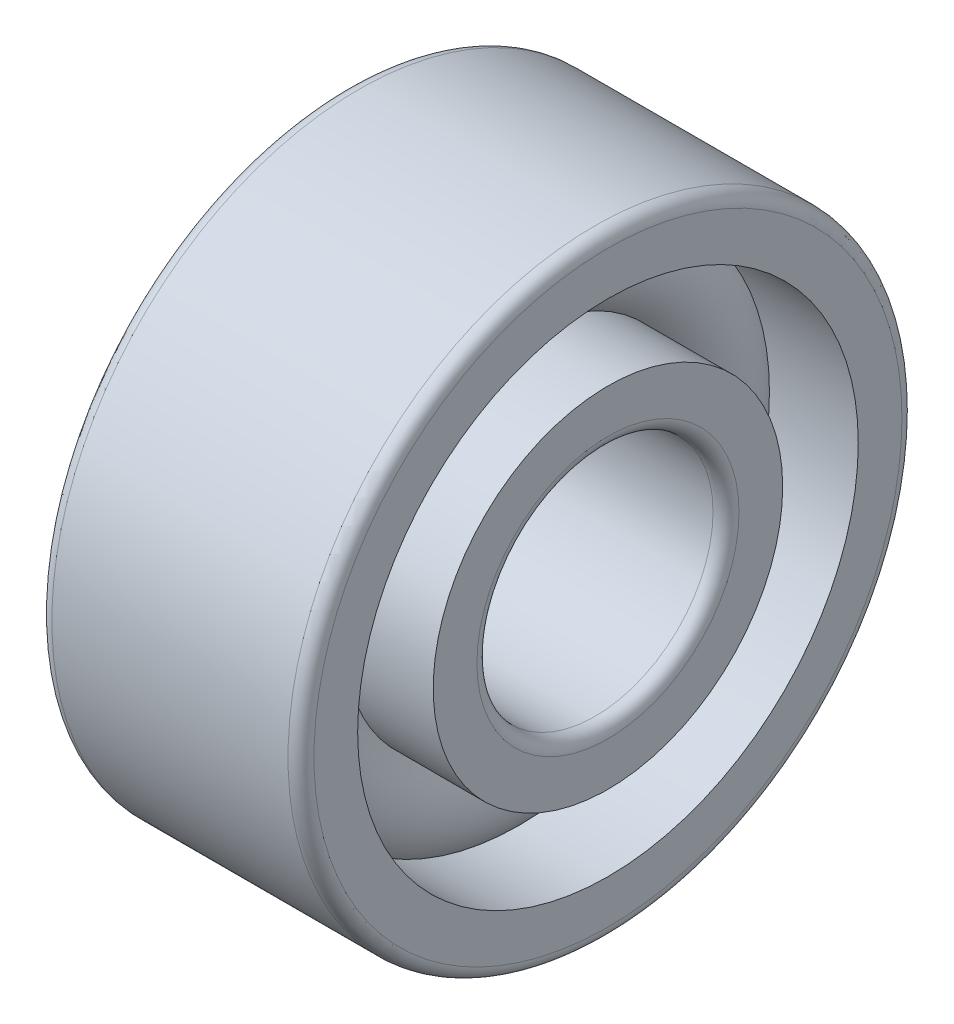
SolidWorks part; units mm, degrees
ref_plane "Plane1" through (0, 0, 0) normal (0, 0, 1) x (1, 0, 0)
ref_plane "Plane2" through (0, 0, 0) normal (0, 1, 0) x (1, 0, 0)
ref_plane "Plane3" through (0, 0, 0) normal (1, 0, 0) x (0, 0, -1)
sketch "Clipboard" plane through (0, 0, 0) normal (0, 0, 1) x (1, 0, 0)
  line L0 (-10, 0) -> (10, 0) construction
  line L1 (0, 0) -> (22.3471, -0.7804)
  line L2 (0, 0) -> (17.989, 0.6282)
  line L3 (0, 0) -> (22.3471, -0.7804)
  line L4 (0, 0) -> (-22.3573, -0.3902)
  dimension "BallCLRad" = 18
sketch "CagSpiSke" plane through (0, 0, 0) normal (0, 0, 1) x (1, 0, 0)
  line L0 (0.48, 17.2) -> (0.48, 18.8)
  line L1 (0.48, 18.8) -> (-0.48, 18.8)
  line L2 (-0.48, 18.8) -> (-0.48, 17.2)
  line L3 (-0.48, 17.2) -> (0.48, 17.2)
  line L4 (-20.6375, 0) -> (20.6375, 0) construction
  line L5 (0, 0) -> (0, 23.7692) construction
  dimension "OD" = 37.6
  dimension "ID" = 34.4
revolve "CageSpine" add sketch "CagSpiSke" angle 0.001 about L4 reverse direction yes
ref_axis "Axis1" through (-50, 0, 0) along (1, 0, 0)
sketch "CagBalSke" plane through (0, 0, 0) normal (0, 0, 1) x (1, 0, 0)
  line L0 (-5.28, 18) -> (5.28, 18)
  line L1 (-1.905, 18) -> (1.905, 18) construction
  line L2 (-10, 0) -> (10, 0) construction
  line L3 (0, 0) -> (0, 24) construction
  arc A0 (5.28, 18) -> (-5.28, 18) centre (0, 18) cw
  dimension "BallCLRad" = 18
revolve "CageBall" [suppressed] add sketch "CagBalSke" angle 360 about L1 reverse direction yes
pattern_circular "CageBalls" [suppressed] count 2 every 180 about axis through (-50, 0, 0) along (1, 0, 0)
sketch "CagTrmODSke" plane through (0, 0, 0) normal (0, 0, 1) x (1, 0, 0)
  line L0 (5.281, 18.8) -> (5.281, 23.281)
  line L1 (5.281, 23.281) -> (-5.281, 23.281)
  line L2 (-5.281, 23.281) -> (-5.281, 18.8)
  line L3 (-5.281, 18.8) -> (5.281, 18.8)
  line L4 (-20.6375, 0) -> (20.6375, 0) construction
  line L5 (0, 0) -> (0, 25) construction
  dimension "Width" = 10.562
  dimension "ID" = 37.6
  dimension "OD" = 46.562
revolve "CageTrimOD" [suppressed] cut sketch "CagTrmODSke" angle 360 about L4 reverse direction yes
sketch "CagTrmIDSke" plane through (0, 0, 0) normal (0, 0, 1) x (1, 0, 0)
  line L0 (5.281, 12.721) -> (5.281, 17.2)
  line L1 (5.281, 17.2) -> (-5.281, 17.2)
  line L2 (-5.281, 17.2) -> (-5.281, 12.721)
  line L3 (-5.281, 12.721) -> (5.281, 12.721)
  line L4 (-20.6375, 0) -> (20.6375, 0) construction
  line L5 (0, 0) -> (0, 25) construction
  dimension "Width" = 10.562
  dimension "ID" = 25.442
  dimension "OD" = 34.4
revolve "CageTrimID" [suppressed] cut sketch "CagTrmIDSke" angle 360 about L4 reverse direction yes
sketch "BalSimSke" plane through (0, 0, 0) normal (0, 0, 1) x (1, 0, 0)
  line L0 (-10, 0) -> (10, 0) construction
  line L1 (-10, 18) -> (10, 18) construction
  line L2 (0, 0) -> (0, 23) construction
  circle A0 centre (0, 18) radius 4.8
  dimension "BallCLRad" = 18
  dimension "Ball_diameter" = 9.6
revolve "BallsSimplified" add sketch "BalSimSke" angle 360 about L0
sketch "BalDetSke" plane through (0, 0, 0) normal (0, 0, 1) x (1, 0, 0)
  line L0 (-4.8, 18) -> (4.8, 18)
  line L1 (-1.905, 18) -> (1.905, 18) construction
  line L2 (0, 0) -> (0, 25) construction
  arc A0 (4.8, 18) -> (-4.8, 18) centre (0, 18) cw
  dimension "BallCLRad" = 18
  dimension "Ball_diameter" = 9.6
revolve "BallDetailed" [suppressed] add sketch "BalDetSke" angle 360 about L1 reverse direction yes
sketch "InnRacSke" plane through (0, 0, 0) normal (0, 0, 1) x (1, 0, 0)
  line L0 (-3.5441, 14.8) -> (-11.1, 14.8)
  line L1 (-11.1, 14.8) -> (-11.1, 11.1)
  line L2 (-10, 10) -> (10, 10)
  line L3 (11.1, 11.1) -> (11.1, 14.8)
  line L4 (11.1, 14.8) -> (3.5441, 14.8)
  line L5 (-20.6375, 0) -> (20.6375, 0) construction
  line L6 (0, 0) -> (0, 30) construction
  arc A0 (-11.1, 11.1) -> (-10, 10) centre (-10, 11.1) ccw
  arc A1 (10, 10) -> (11.1, 11.1) centre (10, 11.1) ccw
  arc A2 (3.5441, 14.8) -> (-3.5441, 14.8) centre (0, 18) cw
  dimension "BallCLRad" = 18
  dimension "Fillet_radius" = 1.1
  dimension "Ball_diameter" = 9.55
  dimension "ID" = 20
  dimension "OD" = 29.6
  dimension "Width" = 22.2
revolve "InnerRace" add sketch "InnRacSke" angle 360 about L5 reverse direction yes
sketch "OutRacSke" plane through (0, 0, 0) normal (0, 0, 1) x (1, 0, 0)
  line L0 (-3.5441, 21.2) -> (-11.1, 21.2)
  line L1 (-11.1, 21.2) -> (-11.1, 24.9)
  line L2 (-10, 26) -> (10, 26)
  line L3 (11.1, 24.9) -> (11.1, 21.2)
  line L4 (11.1, 21.2) -> (3.5441, 21.2)
  line L5 (-20.6375, 0) -> (20.6375, 0) construction
  line L6 (0, 0) -> (0, 30) construction
  arc A0 (-11.1, 24.9) -> (-10, 26) centre (-10, 24.9) cw
  arc A1 (10, 26) -> (11.1, 24.9) centre (10, 24.9) cw
  arc A2 (3.5441, 21.2) -> (-3.5441, 21.2) centre (0, 18) ccw
  dimension "BallCLRad" = 18
  dimension "Fillet_radius" = 1.1
  dimension "Ball_diameter" = 9.55
  dimension "Width" = 22.2
revolve "OuterRace" add sketch "OutRacSke" angle 360 about L5 reverse direction yes
pattern_circular "BallsDetailed" [suppressed] count 2 every 180 about axis through (-50, 0, 0) along (1, 0, 0)
equation "\"BallCLRad@Clipboard\" = ( \"OD@OutRacSke\" + \"ID@InnRacSke\" ) / 4"
equation "\"BallCLRad@BalSimSke\" = \"BallCLRad@Clipboard\""
equation "\"BallCLRad@BalDetSke\" = \"BallCLRad@Clipboard\""
equation "\"BallCLRad@InnRacSke\" = \"BallCLRad@Clipboard\""
equation "\"BallCLRad@OutRacSke\" = \"BallCLRad@Clipboard\""
equation "\"Ball_diameter@InnRacSke\" = \"Ball_diameter@BalDetSke\" - 0.05"
equation "\"Ball_diameter@OutRacSke\" = \"Ball_diameter@BalDetSke\" - 0.05"
equation "\"Ball_diameter@BalSimSke\" = \"Ball_diameter@BalDetSke\""
equation "\"Width@OutRacSke\" = \"Width@InnRacSke\""
equation "\"Fillet_radius@OutRacSke\" = \"Fillet_radius@InnRacSke\""
equation "\"Max_count@Clipboard\" = int( 3.14159265 / atn(( \"Ball_diameter@BalDetSke\" / 2) / sqr( \"BallCLRad@Clipboard\"  *  \"BallCLRad@Clipboard\" - ( \"Ball_diameter@BalDetSke\" / 2) *  ( \"Ball_diameter@BalDetSke\" / 2))))"
equation "\"Max_count@Clipboard\" = ((sgn( \"Max_count@Clipboard\" - \"Count@Clipboard\" )-1)*( \"Max_count@Clipboard\" - \"Count@Clipboard\" ))/-2+ \"Count@Clipboard\""
equation "\"Count@BallsDetailed\" = int( \"Show_count@Clipboard\" ) "
equation "\"Count@BallsDetailed\" = ((sgn( \"Count@BallsDetailed\" - \"Max_count@Clipboard\" )-1)*( \"Count@BallsDetailed\" - \"Max_count@Clipboard\" ))/-2+ \"Max_count@Clipboard\""
equation "\"Count@BallsDetailed\" = ((sgn( \"Count@BallsDetailed\" - \"Min_count@Clipboard\" )+1)*( \"Count@BallsDetailed\" - \"Min_count@Clipboard\"))/2 +\"Min_count@Clipboard\""
equation "\"Angle@BallsDetailed\" = 360.0 / \"Max_count@Clipboard\""
equation "\"BallCLRad@CagBalSke\" = \"BallCLRad@Clipboard\""
equation "\"Count@CageBalls\" = \"Count@BallsDetailed\""
equation "\"Angle@CageBalls\" = \"Angle@BallsDetailed\""
equation "\"Angle@CageSpine\" =  \"Angle@CageBalls\" * ( \"Count@CageBalls\" -1 + int( \"Count@CageBalls\" / \"Max_count@Clipboard\" ) )  + 0.001 -  int( \"Count@CageBalls\" / \"Max_count@Clipboard\" ) * 0.001"
equation "\"Angle@CageSpine\" =  \"Angle@CageSpine\" * int( \"Min_count@Clipboard\" / 2) + int(1 / \"Min_count@Clipboard\")  * 0.001"
equation "\"CageWallOD@CagBalSke\" =  \"Ball_diameter@BalDetSke\" * 1.1"
equation "\"Thickness@CagSpiSke\" =  \"Ball_diameter@BalDetSke\" * 0.1"
equation "\"OD@CagTrmODSke\" = \"BallCLRad@Clipboard\" * 2 + \"CageWallOD@CagBalSke\" + 0.002"
equation "\"ID@CagTrmODSke\" = \"BallCLRad@Clipboard\" * 2 + \"Ball_diameter@BalDetSke\" / 6"
equation "\"OD@CagTrmIDSke\" = \"BallCLRad@Clipboard\" * 2 - \"Ball_diameter@BalDetSke\" / 6"
equation "\"ID@CagTrmIDSke\" = \"BallCLRad@Clipboard\" * 2 - \"CageWallOD@CagBalSke\" + 0.002"
equation "\"OD@CagSpiSke\" = \"ID@CagTrmODSke\""
equation "\"ID@CagSpiSke\" = \"OD@CagTrmIDSke\""
equation "\"Width@CagTrmODSke\" = \"CageWallOD@CagBalSke\" + 0.002"
equation "\"Width@CagTrmIDSke\" = \"CageWallOD@CagBalSke\" + 0.002"
